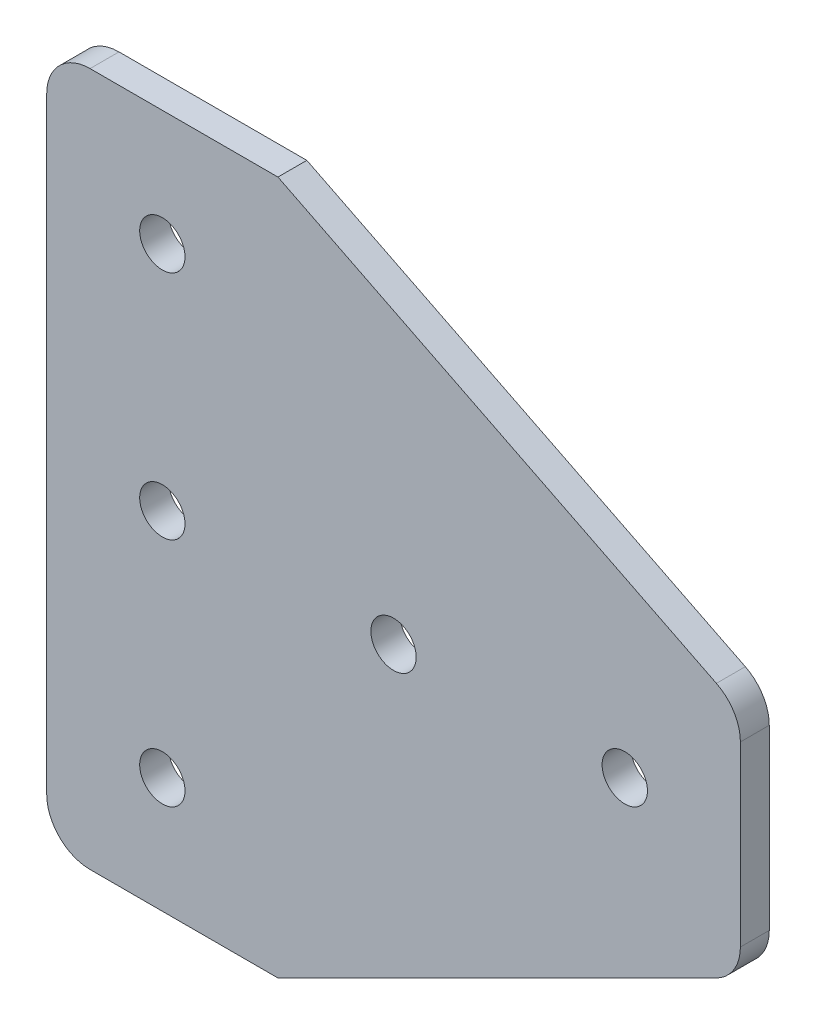
SolidWorks part; units mm, degrees
material "6061-T6 (SS)"
ref_plane "Front Plane" through (0, 0, 0) normal (0, 0, 1) x (1, 0, 0)
ref_plane "Top Plane" through (0, 0, 0) normal (0, 1, 0) x (1, 0, 0)
ref_plane "Right Plane" through (0, 0, 0) normal (1, 0, 0) x (0, 0, -1)
sketch "Sketch1" plane through (0, 0, 0) normal (0, 0, 1) x (1, 0, 0)
  line L0 (0, 0) -> (0, 76.2)
  line L1 (0, 76.2) -> (25.4, 76.2)
  line L4 (76.2, 50.8) -> (76.2, 25.4)
  line L7 (25.4, 0) -> (0, 0)
  line L8 (76.2, 38.1) -> (0, 38.1) construction
  line L9 (25.4, 76.2) -> (76.2, 50.8)
  line L10 (76.2, 25.4) -> (25.4, 0)
  line L11 (25.4, 72.0126) -> (69.6049, 51.5756)
  line L12 (69.6049, 51.5756) -> (26.0024, 51.5756)
  line L13 (26.0024, 51.5756) -> (25.4, 72.0126)
  circle A0 centre (12.7, 63.5) radius 2.4892
  circle A1 centre (12.7, 38.1) radius 2.4892
  circle A2 centre (12.7, 12.7) radius 2.4892
  circle A3 centre (38.1, 38.1) radius 2.4892
  circle A5 centre (63.5, 38.1) radius 2.4892
  point P5 (69.6049, 51.5756)
  point P13 (12.7, 76.2)
  dimension "D5" = 4.9784
  dimension "D7" = 3
  dimension "D1" = 25.4
  dimension "D2" = 76.2
  dimension "D4" = 76.2
  dimension "D6" = 12.7
  dimension "D8" = 25.4
  dimension "D9" = 25.4
  dimension "D10" = 25.4
extrude "Boss-Extrude1" add sketch "Sketch1" along normal mid plane 3.175 contours L0 L1 L9 L4 L10 L7 | A0 | A2 | A1 | A3 | A5
fillet "Fillet1" radius 4.7625 4 edges at (0, 0, 0) (0, 76.2, 0) (76.2, 25.4, 0) (76.2, 50.8, 0)
